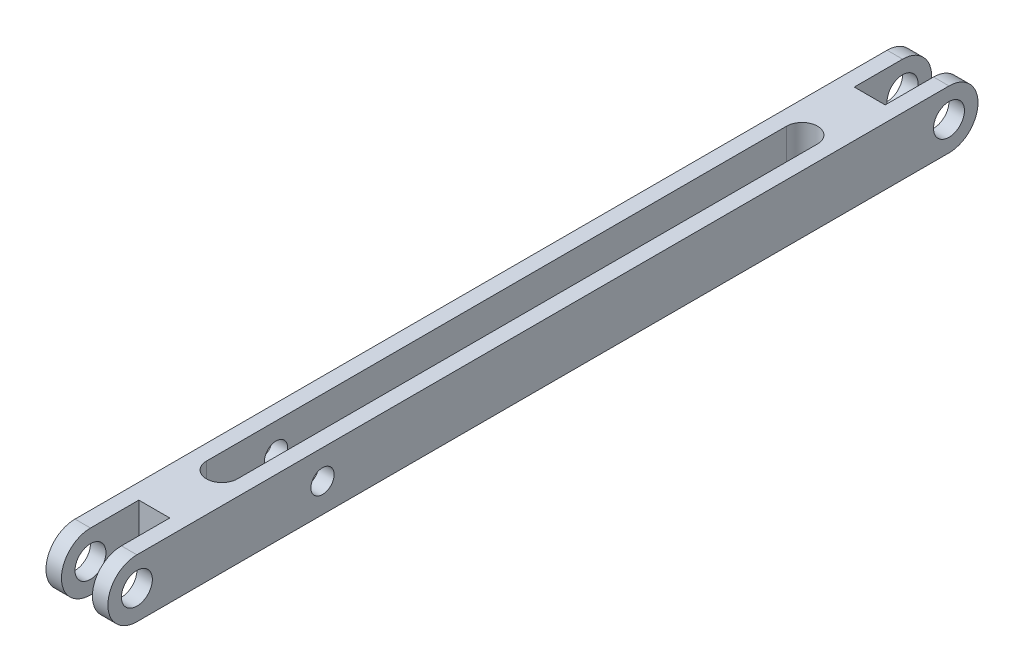
SolidWorks part; units mm, degrees
material "ABS"
ref_plane "前视基准面" through (0, 0, 0) normal (0, 0, 1) x (1, 0, 0)
ref_plane "上视基准面" through (0, 0, 0) normal (0, 1, 0) x (1, 0, 0)
ref_plane "右视基准面" through (0, 0, 0) normal (1, 0, 0) x (0, 0, -1)
sketch "草图2" plane through (0, 0, 0) normal (1, 0, 0) x (0, 0, -1)
  line L0 (-105, 7.5) -> (-105, -7.5) construction
  line L1 (-105, -7.5) -> (105, -7.5)
  line L3 (-105, 7.5) -> (105, 7.5)
  line L5 (-105, -7.5) -> (105, 7.5) construction
  line L6 (-105, 7.5) -> (105, -7.5) construction
  line L7 (105, 7.5) -> (105, -7.5) construction
  arc A0 (-105, 7.5) -> (-105, -7.5) centre (-105, 0) ccw
  arc A1 (105, 7.5) -> (105, -7.5) centre (105, 0) cw
  point P0 (0, 0)
  dimension "D1" = 15
  dimension "D2" = 210
extrude "凸台-拉伸1" add sketch "草图2" along normal blind 16
sketch "草图3" plane through (0, 7.5, 0) normal (0, 1, 0) x (1, 0, 0)
  line L1 (4, -112.5) -> (4, -92.5)
  line L2 (0, -112.5) -> (16, -112.5) construction
  line L3 (4, -92.5) -> (12, -92.5)
  line L4 (12, -92.5) -> (12, -112.5)
  line L5 (12, -112.5) -> (4, -112.5)
  line L6 (0, 105) -> (0, -105) construction
  line L7 (16, 105) -> (16, -105) construction
  line L10 (4, 112.5) -> (12, 112.5)
  line L14 (4, 112.5) -> (4, 92.5)
  line L15 (4, 92.5) -> (12, 92.5)
  line L16 (12, 92.5) -> (12, 112.5)
  line L17 (16, 105) -> (0, 105) construction
  dimension "D1" = 4
  dimension "D2" = 4
  dimension "D3" = 20
  dimension "D4" = 8
  dimension "D5" = 20
  dimension "D6" = 7.5
  dimension "D7" = 4
extrude "切除-拉伸1" cut sketch "草图3" against normal through all
sketch "草图4" plane through (16, 0, 0) normal (1, 0, 0) x (0, 0, -1)
  circle A0 centre (-105, 0) radius 4
  circle A1 centre (105, 0) radius 4
  dimension "D1" = 8
  dimension "D2" = 8
extrude "切除-拉伸2" cut sketch "草图4" against normal through all
sketch "草图5" plane through (0, -7.5, 0) normal (0, -1, 0) x (1, 0, 0)
  line L0 (8, 75) -> (8, -75) construction
  line L1 (12, 75) -> (12, -75)
  line L2 (4, 75) -> (4, -75)
  line L3 (0, 0) -> (8, 0) construction
  line L4 (0, 105) -> (0, -105) construction
  arc A0 (12, 75) -> (4, 75) centre (8, 75) ccw
  arc A1 (4, -75) -> (12, -75) centre (8, -75) ccw
  point P2 (8, 0)
  dimension "D1" = 8
  dimension "D2" = 8
  dimension "D3" = 150
extrude "切除-拉伸3" cut sketch "草图5" against normal through all
sketch "草图6" plane through (0, 0, 0) normal (-1, 0, 0) x (0, 0, 1)
  line L0 (57, 0) -> (0, 0) construction
  circle A1 centre (57, 0) radius 3
  circle A3 centre (105, 0) radius 4 construction
  point P3 (43.4753, 0)
  dimension "D1" = 48
  dimension "D2" = 6
extrude "切除-拉伸4" cut sketch "草图6" against normal through all
